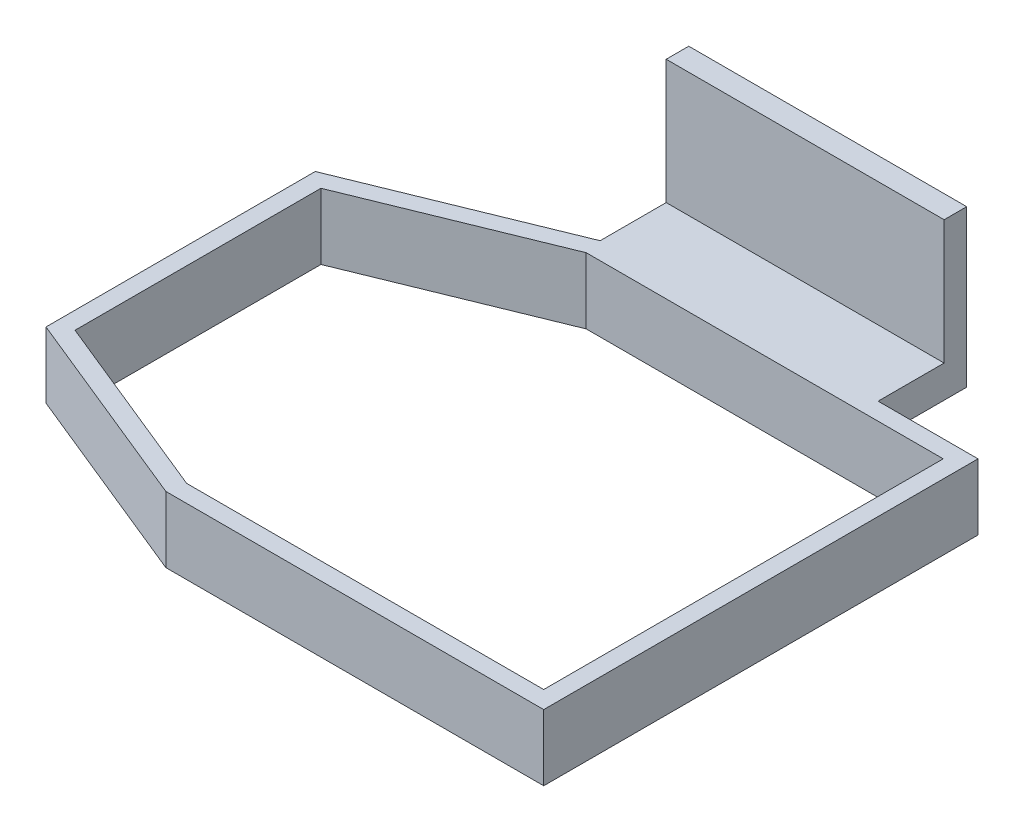
SolidWorks part; units mm, degrees
ref_plane "前视基准面" through (0, 0, 0) normal (0, 0, 1) x (1, 0, 0)
ref_plane "上视基准面" through (0, 0, 0) normal (0, 1, 0) x (1, 0, 0)
ref_plane "右视基准面" through (0, 0, 0) normal (1, 0, 0) x (0, 0, -1)
sketch "草图1" plane through (0, 0, 0) normal (0, 0, 1) x (1, 0, 0)
  line L1 (-16, -9) -> (16, -9)
  line L2 (-16, -9) -> (-16, 9)
  line L3 (-16, 9) -> (16, 9)
  line L4 (16, -9) -> (16, 9)
  line L5 (-16, -9) -> (16, 9) construction
  line L6 (-16, 9) -> (16, -9) construction
  point P0 (0, 0)
  dimension "D1" = 32
  dimension "D2" = 18
extrude "凸台-拉伸1" add sketch "草图1" along normal blind 2.6
sketch "草图2" plane through (0, 0, 2.6) normal (0, 0, 1) x (1, 0, 0)
  line L0 (-16, 9) -> (-16, -9) construction
  line L1 (16, -9) -> (-16, -9)
  line L2 (16, -9) -> (16, -5.2913)
  line L3 (16, -5.2913) -> (-16, -5.2913)
  line L4 (-16, -9) -> (-16, -5.2913)
extrude "凸台-拉伸2" add sketch "草图2" along normal blind 7.6
sketch "草图3" plane through (0, -5.2913, 0) normal (0, 1, 0) x (1, 0, 0)
  line L0 (27.5, -10.2) -> (-16, -10.2)
  line L1 (-16, -10.2) -> (-39.3, -19.7)
  line L2 (-39.3, -19.7) -> (-39.3, -50.7)
  line L3 (-32.8864, -35.2) -> (25.8787, -35.2) construction
  line L4 (27.5, -10.2) -> (27.5, -60.2)
  line L5 (-16, -60.2) -> (-39.3, -50.7)
  line L6 (27.5, -60.2) -> (-16, -60.2)
  line L7 (16, -10.2) -> (16, -2.6) construction
  line L8 (-16, -10.2) -> (-16, -2.6) construction
  line L9 (25.5, -12.2) -> (-15.6079, -12.2)
  line L10 (-15.6079, -12.2) -> (-37.3, -21.0444)
  line L11 (-37.3, -21.0444) -> (-37.3, -49.3556)
  line L12 (-15.6079, -58.2) -> (-37.3, -49.3556)
  line L13 (25.5, -58.2) -> (-15.6079, -58.2)
  line L14 (25.5, -12.2) -> (25.5, -58.2)
  point P8 (0, 0)
  point P10 (27.5, -35.2)
  dimension "D1" = 50
  dimension "D2" = 11.5
  dimension "D3" = 23.3
  dimension "D4" = 31
  dimension "D5" = 2
extrude "凸台-拉伸3" add sketch "草图3" against normal blind 7.6
